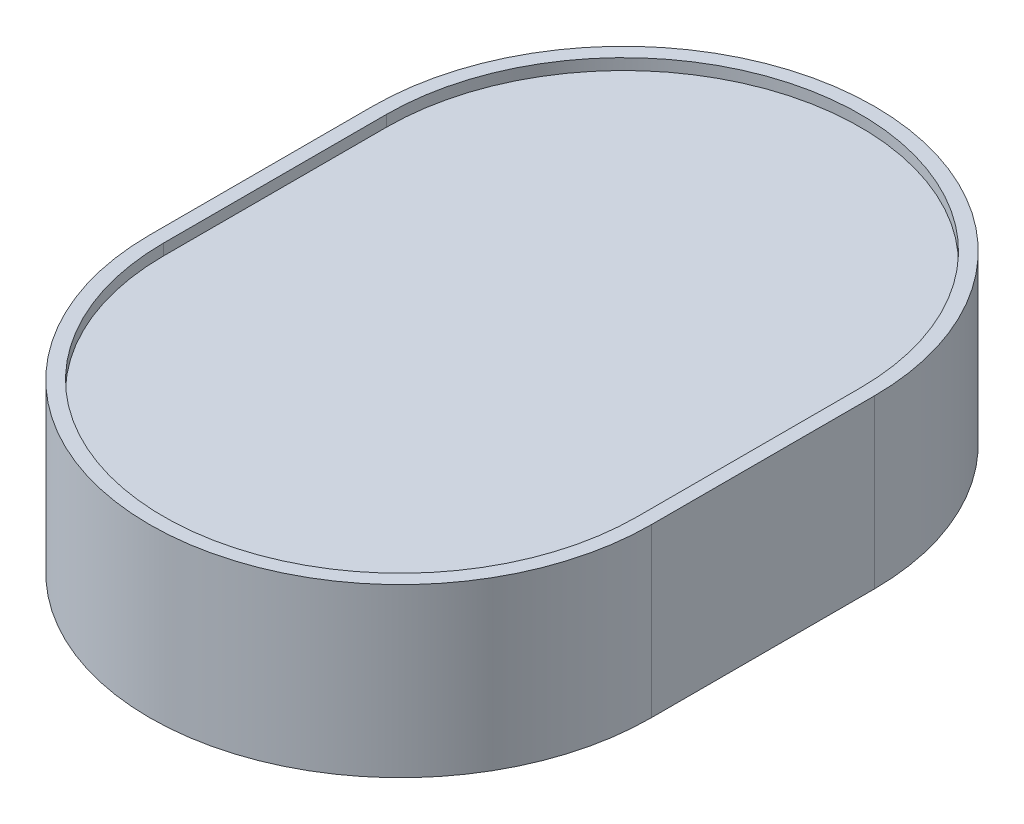
SolidWorks part; units mm, degrees
ref_plane "Front Plane" through (0, 0, 0) normal (0, 0, 1) x (1, 0, 0)
ref_plane "Top Plane" through (0, 0, 0) normal (0, 1, 0) x (1, 0, 0)
ref_plane "Right Plane" through (0, 0, 0) normal (1, 0, 0) x (0, 0, -1)
sketch "Sketch1" plane through (0, 0, 0) normal (0, 1, 0) x (1, 0, 0)
  line L0 (0, -4) -> (0, 4) construction
  line L1 (-9, -4) -> (-9, 4)
  line L2 (9, -4) -> (9, 4)
  arc A0 (-9, -4) -> (9, -4) centre (0, -4) ccw
  arc A1 (9, 4) -> (-9, 4) centre (0, 4) ccw
  point P2 (0, 0)
  point P8 (0, 0)
extrude "Boss-Extrude1" add sketch "Sketch1" along normal blind 6
sketch "Sketch2" plane through (0, 6, 0) normal (0, 1, 0) x (1, 0, 0)
  line L0 (0, -4) -> (0, 4) construction
  line L1 (-8.5, -4) -> (-8.5, 4)
  line L2 (8.5, -4) -> (8.5, 4)
  arc A1 (-8.5, -4) -> (8.5, -4) centre (0, -4) ccw
  arc A2 (8.5, 4) -> (-8.5, 4) centre (0, 4) ccw
  point P3 (0, 0)
extrude "Cut-Extrude1" cut sketch "Sketch2" against normal blind 0.4
